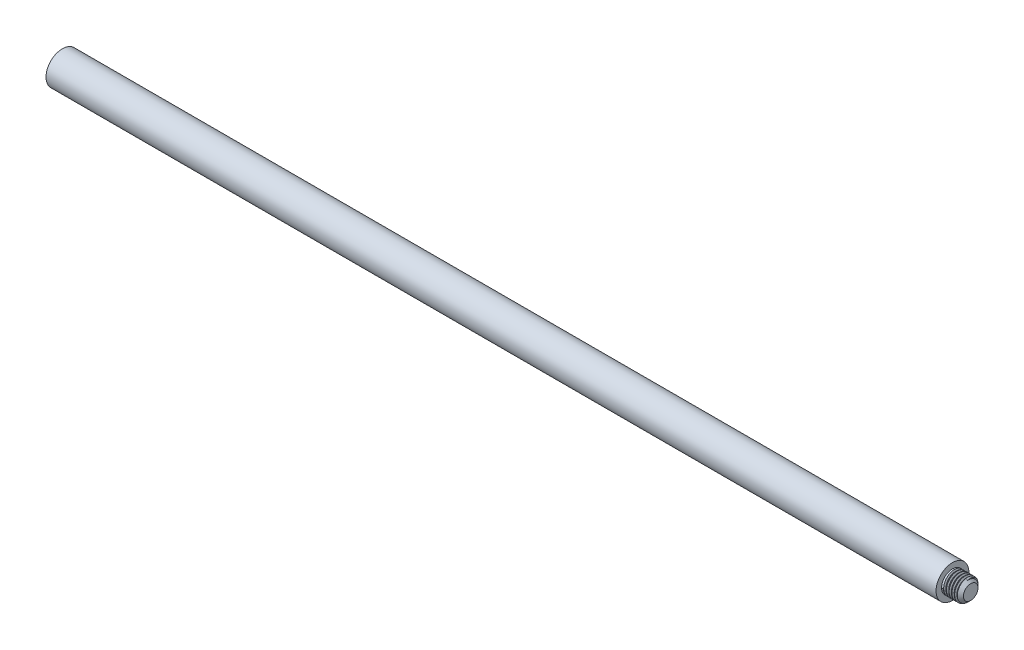
SolidWorks part; units mm, degrees
ref_plane "Płaszczyzna przednia" through (0, 0, 0) normal (0, 0, 1) x (1, 0, 0)
ref_plane "Płaszczyzna górna" through (0, 0, 0) normal (0, 1, 0) x (1, 0, 0)
ref_plane "Płaszczyzna prawa" through (0, 0, 0) normal (1, 0, 0) x (0, 0, -1)
sketch "Szkic1" plane through (0, 0, 0) normal (1, 0, 0) x (0, 0, -1)
  circle A0 centre (0, 0) radius 9
  dimension "D1" = 18
extrude "Dodanie-wyciągnięcie1" add sketch "Szkic1" along normal blind 488
sketch "Szkic2" plane through (0, 0, 0) normal (-1, 0, 0) x (0, 0, 1)
  circle A0 centre (0, 0) radius 6
  dimension "D1" = 12
extrude "Wytnij-wyciągnięcie1" cut sketch "Szkic2" against normal blind 12
thread "Gwint1" pitch 1.5 method extrude profile "Profil gwintu1" start angle 0, offset 0, length 0, pitch 1.5, diameter 12
ref_plane "Płaszczyzna1" through (0, 0, -6) normal (0, -1, 0) x (0, 0, -1)
sketch "Profil gwintu1" plane through (0, 0, -6) normal (0, -1, 0) x (0, 0, -1)
  line L0 (0, 0) -> (0, 1.5) construction
  line L11 (0, 0) -> (0, 1.3125)
  line L12 (0, 1.3125) -> (-0.8119, 0.8437)
  line L13 (-0.8119, 0.8437) -> (-0.8119, 0.4687)
  line L15 (-0.8119, 0.4687) -> (0, 0)
  line L17 (-0.8119, 0.6562) -> (0, 0.6562) construction
  point P2 (0, 0)
  dimension "Pitch" = 1.5
  dimension "Profile_Angle" = 60
  dimension "Profile_Land" = 0.375
  dimension "Profile_Height" = 0.8119
sketch "Szkic5" plane through (488, 0, 0) normal (1, 0, 0) x (0, 0, -1)
  circle A0 centre (0, 0) radius 6
  dimension "D1" = 12
extrude "Dodanie-wyciągnięcie2" add sketch "Szkic5" along normal blind 10
chamfer "Sfazowanie1" distance 2 angle 45 1 edges at (498, 0, -6)
thread "Gwint2" pitch 1.5 method cut profile "Profil gwintu3" start angle 0, offset 5, length 12, pitch 1.5, diameter 12
ref_plane "Płaszczyzna3" through (501, 0, 6) normal (0, -1, 0) x (0, 0, 1)
sketch "Profil gwintu3" plane through (501, 0, 6) normal (0, -1, 0) x (0, 0, 1)
  line L0 (0, 0) -> (0, 1.5) construction
  line L11 (0, 0) -> (0, 1.3125)
  line L12 (0, 1.3125) -> (-0.8119, 0.8437)
  line L13 (-0.8119, 0.8437) -> (-0.8119, 0.4687)
  line L15 (-0.8119, 0.4687) -> (0, 0)
  line L17 (-0.8119, 0.6562) -> (0, 0.6562) construction
  point P2 (0, 0)
  dimension "Pitch" = 1.5
  dimension "Profile_Angle" = 60
  dimension "Profile_Land" = 0.375
  dimension "Profile_Height" = 0.8119
